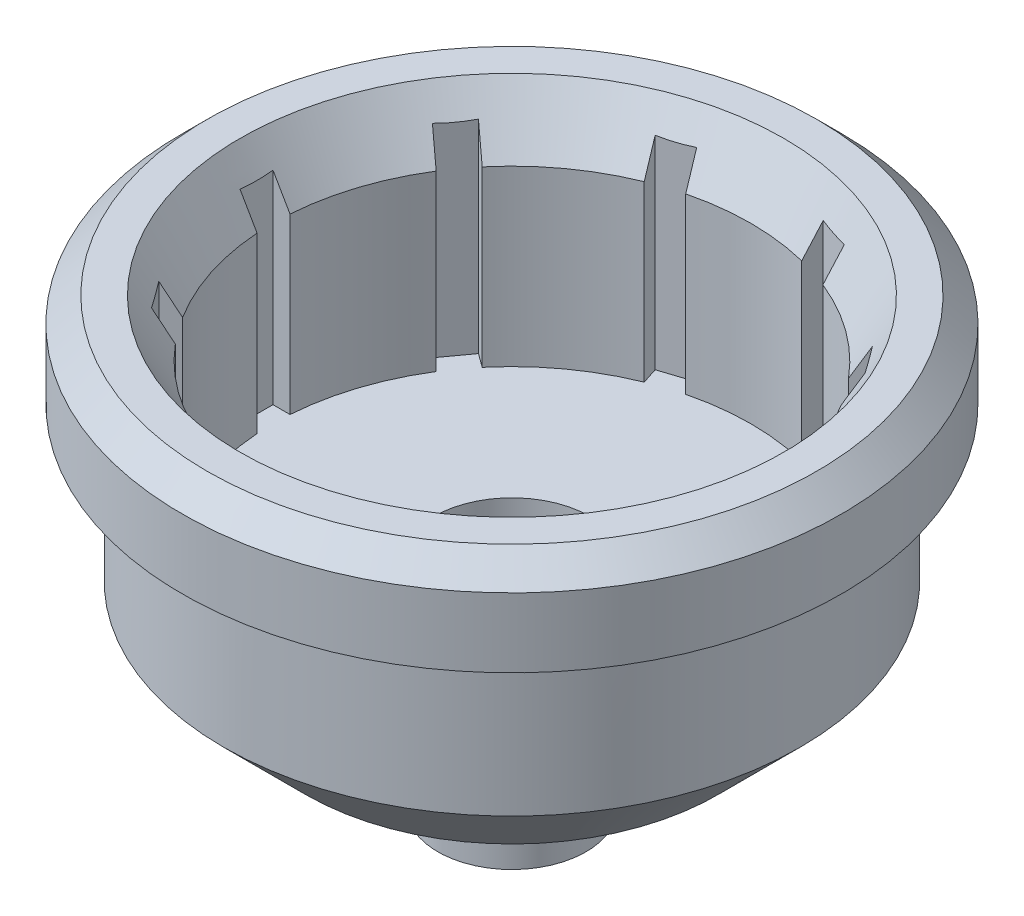
SolidWorks part; units mm, degrees
ref_plane "Front Plane" through (0, 0, 0) normal (0, 0, 1) x (1, 0, 0)
ref_plane "Top Plane" through (0, 0, 0) normal (0, 1, 0) x (1, 0, 0)
ref_plane "Right Plane" through (0, 0, 0) normal (1, 0, 0) x (0, 0, -1)
sketch "Sketch1" plane through (0, 0, 0) normal (0, 0, 1) x (1, 0, 0)
  line L0 (0, 0) -> (-2.5, 0) construction
  line L1 (-2.5, 0) -> (-2.5, 9)
  line L2 (-2.5, 9) -> (-4.75, 9)
  line L3 (-4.75, 9) -> (-4.75, 13)
  line L4 (-4.75, 13) -> (-14.5, 13)
  line L5 (-14.5, 13) -> (-14.5, 27)
  line L6 (-14.5, 27) -> (-20, 27)
  line L7 (-20, 27) -> (-20, 21.3)
  line L8 (-20, 21.3) -> (-17.5, 21.3)
  line L9 (-17.5, 21.3) -> (-17.5, 7)
  line L10 (-17.5, 7) -> (-6.5, 7)
  line L11 (-6.5, 7) -> (-6.5, 6)
  line L12 (-6.5, 6) -> (-4.5, 6)
  line L13 (-4.5, 6) -> (-4.5, 0)
  line L14 (-4.5, 0) -> (-2.5, 0)
  line L15 (0, 0) -> (0, 40) construction
  dimension "D1" = 5
  dimension "D2" = 9
  dimension "D3" = 2
  dimension "D4" = 6
  dimension "D5" = 9.5
  dimension "D6" = 4
  dimension "D7" = 3
  dimension "D8" = 1
  dimension "D9" = 29
  dimension "D10" = 35
  dimension "D11" = 40
  dimension "D12" = 5.7
  dimension "D13" = 14
revolve "Revolve1" add sketch "Sketch1" angle 360 about L15
chamfer "Chamfer1" distance 2 angle 60 1 edges at (0, 27, -14.5) first distance on face at (0, 27, -20)
chamfer "Chamfer2" distance 1.5 angle 45 1 edges at (0, 27, -20)
sketch "Sketch2" plane through (0, 13, 0) normal (0, 1, 0) x (1, 0, 0)
  line L1 (-15.5, -1) -> (15.5, -1)
  line L2 (-15.5, -1) -> (-15.5, 1)
  line L3 (-15.5, 1) -> (15.5, 1)
  line L4 (15.5, -1) -> (15.5, 1)
  line L5 (-15.5, -1) -> (15.5, 1) construction
  line L6 (-15.5, 1) -> (15.5, -1) construction
  point P0 (0, 0)
  dimension "D1" = 2
  dimension "D2" = 31
extrude "Cut-Extrude1" cut sketch "Sketch2" along normal through all
pattern_circular "CirPattern1" count 10 over 360 about axis through (0, 13, 0) along (0, -1, 0) of "Cut-Extrude1"
chamfer "Chamfer3" distance 5 angle 45 1 edges at (0, 7, -17.5)
